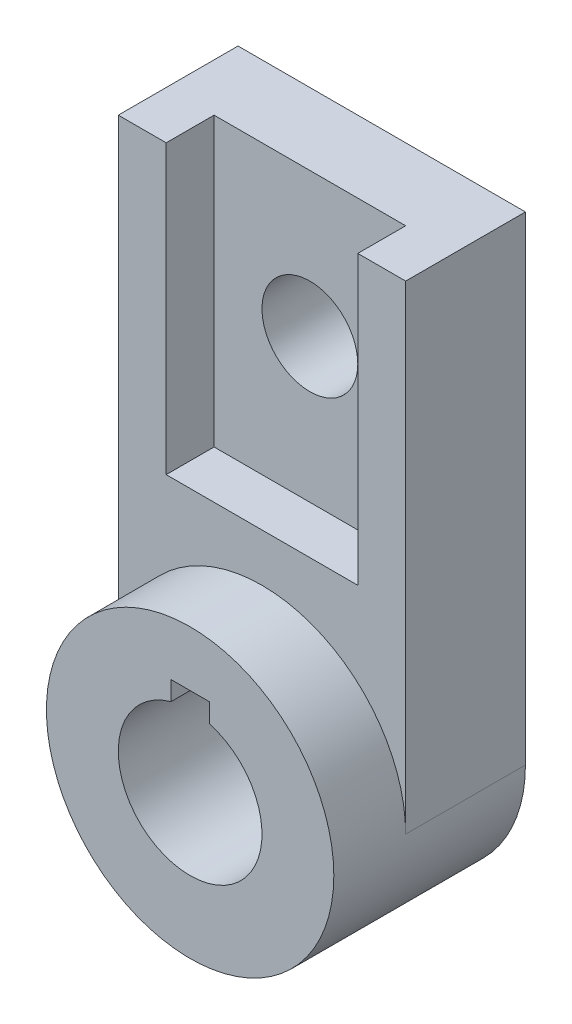
SolidWorks part; units mm, degrees
ref_plane "Front Plane" through (0, 0, 0) normal (1, 0, 0) x (0, 1, 0)
ref_plane "Top Plane" through (0, 0, 0) normal (0, 0, 1) x (0, 1, 0)
ref_plane "Right Plane" through (0, 0, 0) normal (0, 1, 0) x (-1, 0, 0)
sketch "Sketch1" plane through (0, 0, 0) normal (0, 0, 1) x (0, 1, 0)
  line L0 (0, 30) -> (100, 30)
  line L1 (100, 30) -> (100, -30)
  line L2 (100, -30) -> (0, -30)
  circle A0 centre (0, 0) radius 30
  dimension "D1" = 60
  dimension "D2" = 100
extrude "Boss-Extrude1" add sketch "Sketch1" along normal blind 25 contours A0 L2 L1 L0 region at (0, 61.4877, 0)
extrude "Boss-Extrude2" add sketch "Sketch1<3>" along normal blind 40 contours A0 region at (0, 0, 0)
sketch "Sketch1<3>" plane through (0, 0, 0) normal (0, 0, 1) x (0, 1, 0) same geometry as "Sketch1"
sketch "Sketch2" plane through (0, 0, 25) normal (0, 0, 1) x (1, 0, 0)
  line L0 (-30, 100) -> (30, 100) construction
  line L1 (-20, 100) -> (20, 100)
  line L2 (-20, 100) -> (-20, 40)
  line L3 (-20, 40) -> (20, 40)
  line L4 (20, 100) -> (20, 40)
  point P6 (0, 40)
  dimension "D1" = 60
  dimension "D2" = 40
extrude "Cut-Extrude1" cut sketch "Sketch2" against normal blind 10
sketch "Sketch3" plane through (0, 0, 15) normal (0, 0, 1) x (1, 0, 0)
  line L0 (20, 100) -> (-20, 100) construction
  circle A0 centre (0, 70) radius 10
  point P4 (0, 0)
  dimension "D2" = 20
  dimension "D1" = 30
extrude "Cut-Extrude2" cut sketch "Sketch3" against normal through all both and the other way through all
sketch "Sketch4" plane through (0, 0, 40) normal (0, 0, 1) x (1, 0, 0)
  line L0 (-4, 18.4568) -> (4, 18.4568)
  line L1 (4, 18.4568) -> (4, 14.4568)
  line L2 (-4, 18.4568) -> (-4, 14.4568)
  arc A0 (-4, 14.4568) -> (4, 14.4568) centre (0, 0) ccw
  point P5 (0, 0)
  point P8 (0, 18.4568)
  dimension "D1" = 30
  dimension "D2" = 8
  dimension "D3" = 4
extrude "Cut-Extrude3" cut sketch "Sketch4" against normal through all both and the other way through all
